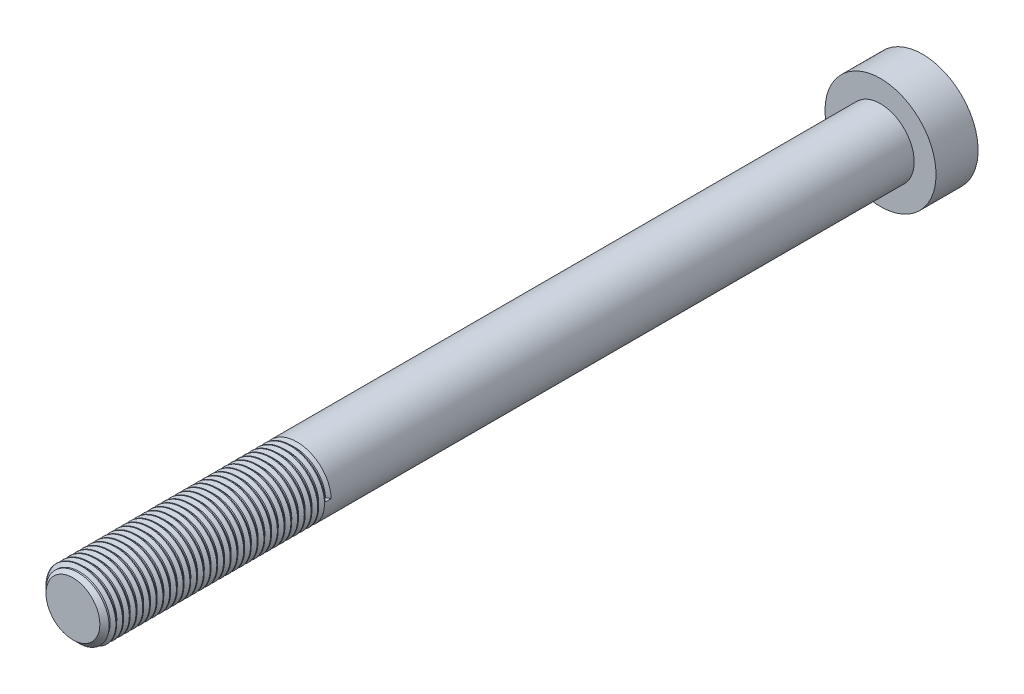
SolidWorks part; units mm, degrees
ref_plane "Спереди" through (0, 0, 0) normal (0, 0, 1) x (1, 0, 0)
ref_plane "Сверху" through (0, 0, 0) normal (0, 1, 0) x (1, 0, 0)
ref_plane "Справа" through (0, 0, 0) normal (1, 0, 0) x (0, 0, -1)
sketch "Эскиз1" plane through (0, 0, 0) normal (0, 0, 1) x (1, 0, 0)
  circle A0 centre (0, 0) radius 10
  dimension "D1" = 20
extrude "Бобышка-Вытянуть1" add sketch "Эскиз1" along normal blind 240
sketch "Эскиз2" plane through (0, 0, 0) normal (0, 0, -1) x (-1, 0, 0)
  circle A0 centre (0, 0) radius 16.5
  dimension "D1" = 33
extrude "Бобышка-Вытянуть2" add sketch "Эскиз2" along normal blind 12.5
chamfer "Фаска1" distance 2 angle 45 1 edges at (10, 0, 240)
thread "Резьба1" pitch 2 method cut profile "Профиль резьбы1" start angle 0, offset 0, length 65, pitch 2, diameter 20
ref_plane "Плоскость1" through (-10, 0, 240) normal (0, -1, 0) x (-1, 0, 0)
sketch "Профиль резьбы1" plane through (-10, 0, 240) normal (0, -1, 0) x (-1, 0, 0)
  line L0 (0, 0) -> (0, 2) construction
  line L11 (0, 0) -> (0, 1.75)
  line L12 (0, 1.75) -> (-1.0825, 1.125)
  line L13 (-1.0825, 1.125) -> (-1.0825, 0.625)
  line L15 (-1.0825, 0.625) -> (0, 0)
  line L17 (-1.0825, 0.875) -> (0, 0.875) construction
  point P2 (0, 0)
  dimension "Pitch" = 2
  dimension "Profile_Angle" = 60
  dimension "Profile_Land" = 0.5
  dimension "Profile_Height" = 1.0825
